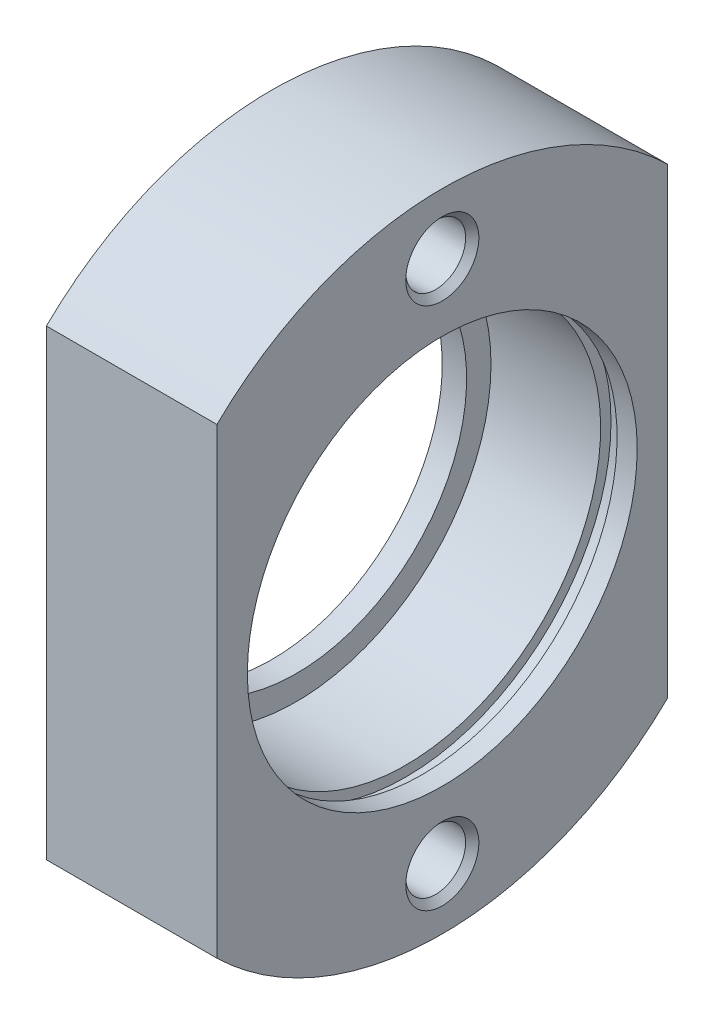
SolidWorks part; units mm, degrees
ref_plane "Front Plane" through (0, 0, 0) normal (0, 0, 1) x (1, 0, 0)
ref_plane "Top Plane" through (0, 0, 0) normal (0, 1, 0) x (1, 0, 0)
ref_plane "Right Plane" through (0, 0, 0) normal (1, 0, 0) x (0, 0, -1)
ref_plane "Plane1" through (0, 0, 0) normal (1, 0, 0) x (0, 0, -1)
sketch "Sketch1" plane through (0, 0, 0) normal (1, 0, 0) x (0, 0, -1)
  line L0 (-18.5, 18.9737) -> (-18.5, -18.9737)
  line L1 (18.5, -18.9737) -> (18.5, 18.9737)
  arc A0 (-18.5, -18.9737) -> (18.5, -18.9737) centre (0, 0) ccw
  arc A1 (18.5, 18.9737) -> (-18.5, 18.9737) centre (0, 0) ccw
extrude "Boss-Extrude1" add sketch "Sketch1" against normal blind 7 and the other way blind 7
ref_plane "Plane2" through (0, 0, 0) normal (0, 0, 1) x (1, 0, 0)
sketch "Sketch2" plane through (0, 0, 0) normal (0, 0, 1) x (1, 0, 0)
  line L0 (-7, 0) -> (-7, 14)
  line L1 (-7, 14) -> (-5, 14)
  line L2 (-5, 14) -> (-5, 16)
  line L3 (-5, 16) -> (7, 16)
  line L4 (7, 16) -> (7, 0)
  line L5 (7, 0) -> (-7, 0)
  line L6 (7, 0) -> (-7, 0) construction
revolve "Cut-Revolve1" cut sketch "Sketch2" angle 360 about L6 reverse direction yes
ref_plane "Plane3" through (0, 0, 0) normal (0, 0, 1) x (1, 0, 0)
sketch "Sketch3" plane through (0, 0, 0) normal (0, 0, 1) x (1, 0, 0)
  line L0 (4, 0) -> (4, 16.85)
  line L1 (4, 16.85) -> (5.35, 16.85)
  line L2 (5.35, 16.85) -> (5.35, 0)
  line L3 (5.35, 0) -> (4, 0)
  line L4 (5.35, 0) -> (4, 0) construction
revolve "Cut-Revolve2" cut sketch "Sketch3" angle 360 about L4 reverse direction yes
ref_plane "Plane4" through (0, 0, 0) normal (0, 0, 1) x (1, 0, 0)
sketch "Sketch4" plane through (0, 0, 0) normal (0, 0, 1) x (1, 0, 0)
  line L0 (-7, -21.5) -> (-7, -18.5)
  line L1 (-7, -18.5) -> (-6.4585, -19.0415)
  line L2 (-6.4585, -19.0415) -> (6.4585, -19.0415)
  line L3 (6.4585, -19.0415) -> (7, -18.5)
  line L4 (7, -18.5) -> (7, -21.5)
  line L5 (7, -21.5) -> (-7, -21.5)
  line L6 (7, -21.5) -> (-7, -21.5) construction
revolve "Cut-Revolve3" cut sketch "Sketch4" angle 360 about L6 reverse direction yes
cosmetic thread "Cosmetic Thread1" parameters "D1"=14, "D2"=6
ref_plane "Plane5" through (0, 0, 0) normal (0, 0, 1) x (1, 0, 0)
sketch "Sketch5" plane through (0, 0, 0) normal (0, 0, 1) x (1, 0, 0)
  line L0 (-7, 21.5) -> (-7, 24.5)
  line L1 (-7, 24.5) -> (-6.4585, 23.9585)
  line L2 (-6.4585, 23.9585) -> (6.4585, 23.9585)
  line L3 (6.4585, 23.9585) -> (7, 24.5)
  line L4 (7, 24.5) -> (7, 21.5)
  line L5 (7, 21.5) -> (-7, 21.5)
  line L6 (7, 21.5) -> (-7, 21.5) construction
revolve "Cut-Revolve4" cut sketch "Sketch5" angle 360 about L6 reverse direction yes
cosmetic thread "Cosmetic Thread2" parameters "D1"=14, "D2"=6
